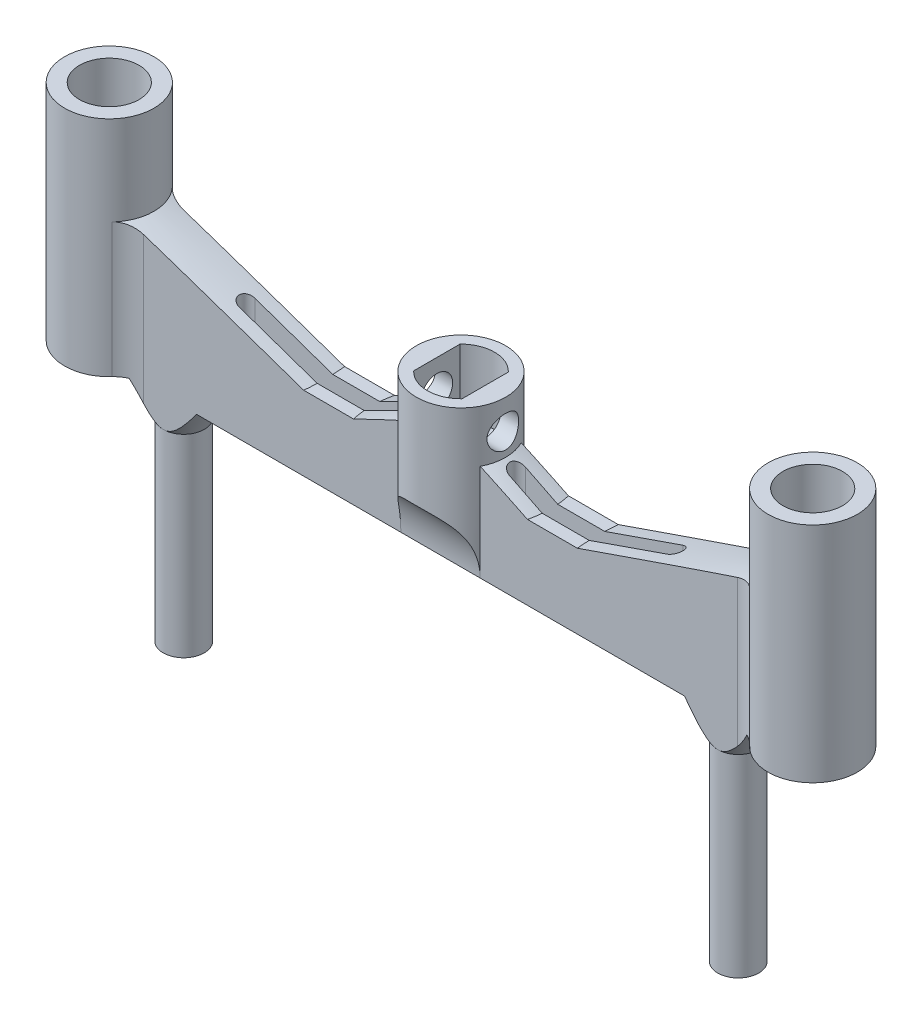
SolidWorks part; units mm, degrees
ref_plane "Front Plane" through (0, 0, 0) normal (0, 0, 1) x (1, 0, 0)
ref_plane "Top Plane" through (0, 0, 0) normal (0, 1, 0) x (1, 0, 0)
ref_plane "Right Plane" through (0, 0, 0) normal (1, 0, 0) x (0, 0, -1)
sketch "Sketch1" plane through (0, 0, 0) normal (0, 1, 0) x (1, 0, 0)
  line L0 (0, 0) -> (-8.0623, 0) construction
  line L1 (37.25, -2.75) -> (37.25, 2.75) construction
  line L2 (0, 0) -> (0, 13.1499) construction
  line L3 (34.5, 0) -> (40, 0) construction
  line L4 (37.25, -2.75) -> (-37.25, -2.75) construction
  line L5 (37.25, 2.75) -> (-37.25, 2.75) construction
  circle A0 centre (-31.5, 0) radius 0.7937 construction
  circle A1 centre (-22.5, 0) radius 0.7937 construction
  circle A2 centre (-37.25, 0) radius 2.75
  circle A3 centre (-37.25, 0) radius 1 construction
  circle A4 centre (37.25, 0) radius 1 construction
  circle A5 centre (37.25, 0) radius 2.75
  circle A8 centre (-22.5, 0) radius 2.75 construction
  circle A9 centre (-13.5, 0) radius 0.7937 construction
  circle A10 centre (-13.5, 0) radius 2.75 construction
  circle A11 centre (-4.5, 0) radius 0.7937 construction
  circle A12 centre (-4.5, 0) radius 2.75 construction
  circle A13 centre (4.5, 0) radius 0.7937 construction
  circle A14 centre (-31.5, 0) radius 2.75 construction
  circle A15 centre (4.5, 0) radius 2.75 construction
  circle A16 centre (13.5, 0) radius 0.7937 construction
  circle A17 centre (13.5, 0) radius 2.75 construction
  circle A18 centre (22.5, 0) radius 0.7937 construction
  circle A19 centre (22.5, 0) radius 2.75 construction
  circle A20 centre (31.5, 0) radius 0.7937 construction
  circle A21 centre (31.5, 0) radius 2.75 construction
  dimension "D1" = 8
extrude "Boss-Extrude1" add sketch "Sketch1" along normal blind 30
ref_plane "Plane1" through (0, 30, 0) normal (0, 1, 0) x (-1, 0, 0)
sketch "Sketch2" plane through (0, 30, 0) normal (0, 1, 0) x (-1, 0, 0)
  line L0 (0, 0) -> (-8.0623, 0) construction
  line L1 (-47.25, -2.75) -> (-47.25, 2.75) construction
  line L2 (0, 0) -> (0, 6.1566) construction
  line L3 (47.25, -2.75) -> (47.25, 2.75) construction
  line L4 (-41.9173, 2.75) -> (41.9173, 2.75)
  line L5 (41.9173, -2.75) -> (-41.9173, -2.75)
  line L6 (7.5915, -1.0438) -> (28.75, -1.0438)
  line L7 (-28.75, 1.0437) -> (-7.5915, 1.0437)
  line L8 (28.75, 1.0437) -> (7.5915, 1.0437)
  line L9 (-7.5915, -1.0438) -> (-28.75, -1.0438)
  arc A0 (-28.75, 1.0437) -> (-28.75, -1.0438) centre (-28.75, 0) ccw
  arc A1 (7.5915, 1.0437) -> (7.5915, -1.0438) centre (7.5915, 0) ccw
  circle A2 centre (-47.25, 0) radius 4
  arc A3 (-7.5915, 1.0437) -> (-7.5915, -1.0438) centre (-7.5915, 0) cw
  arc A4 (41.9173, -2.75) -> (41.9173, 2.75) centre (47.25, 0) ccw
  arc A5 (-41.9173, -2.75) -> (-41.9173, 2.75) centre (-47.25, 0) cw
  arc A8 (28.75, 1.0437) -> (28.75, -1.0438) centre (28.75, 0) cw
  circle A26 centre (47.25, 0) radius 4
extrude "Boss-Extrude2" add sketch "Sketch2" along normal blind 10
ref_plane "Plane2" through (0, 40, 0) normal (0, 1, 0) x (-1, 0, 0)
sketch "Sketch3" plane through (0, 40, 0) normal (0, 1, 0) x (-1, 0, 0)
  line L1 (3.25, -3.1125) -> (3.25, 3.1125) construction
  line L2 (-3.25, -3.1125) -> (-3.25, 3.1125) construction
  arc A0 (3.25, 3.1125) -> (-3.25, 3.1125) centre (0, 0) ccw construction
  circle A1 centre (0, 0) radius 6
  arc A2 (3.25, -3.1125) -> (-3.25, -3.1125) centre (0, 0) cw construction
extrude "Boss-Extrude3" add sketch "Sketch3" along normal blind 1
ref_plane "Plane3" through (0, 0, 0) normal (0, -1, 0) x (1, 0, 0)
hole_wizard "M3x0.5 Tapped Hole4" positions "Sketch28" profile "Sketch27" tap size "M3x0.5" standard "Ansi Metric"
sketch "Sketch28" plane through (0, 0, 0) normal (0, -1, 0) x (1, 0, 0)
  point P0 (37.25, 0)
sketch "Sketch27" plane through (37.25, 0, 0) normal (1, 0, 0) x (0, 0, -1)
  line L0 (0, 0) -> (0, 9.2511)
  line L1 (0, 9.2511) -> (1.25, 8.5)
  line L2 (1.25, 8.5) -> (1.25, 0)
  line L5 (1.25, 0) -> (0, 0)
  line L10 (0, 9.2511) -> (-1.25, 8.5) construction
  line L11 (0, -6.35) -> (0, 107.95) construction
  dimension "Tap Drill Dia." = 2.5
  dimension "Tap Drill Depth" = 8.5
  dimension "Drill Angle" = 118
cosmetic thread "Hole Thread5" parameters "D1"=6, "D2"=3
hole_wizard "M3x0.5 Tapped Hole5" positions "Sketch31" profile "Sketch30" tap size "M3x0.5" standard "Ansi Metric"
sketch "Sketch31" plane through (0, 0, 0) normal (0, -1, 0) x (1, 0, 0)
  point P0 (-37.25, 0)
sketch "Sketch30" plane through (-37.25, 0, 0) normal (1, 0, 0) x (0, 0, -1)
  line L0 (0, 0) -> (0, 9.2511)
  line L1 (0, 9.2511) -> (1.25, 8.5)
  line L2 (1.25, 8.5) -> (1.25, 0)
  line L5 (1.25, 0) -> (0, 0)
  line L10 (0, 9.2511) -> (-1.25, 8.5) construction
  line L11 (0, -6.35) -> (0, 107.95) construction
  dimension "Tap Drill Dia." = 2.5
  dimension "Tap Drill Depth" = 8.5
  dimension "Drill Angle" = 118
cosmetic thread "Hole Thread6" parameters "D1"=6, "D2"=3
ref_plane "Plane4" through (0, 41, 0) normal (0, 1, 0) x (-1, 0, 0)
sketch "Sketch33" plane through (0, 41, 0) normal (0, 1, 0) x (-1, 0, 0)
  line L1 (3.25, -3.1125) -> (3.25, 3.1125)
  line L2 (-3.25, -3.1125) -> (-3.25, 3.1125)
  arc A0 (3.25, 3.1125) -> (-3.25, 3.1125) centre (0, 0) ccw
  circle A1 centre (0, 0) radius 6
  arc A2 (3.25, -3.1125) -> (-3.25, -3.1125) centre (0, 0) cw
extrude "Boss-Extrude4" add sketch "Sketch33" along normal blind 9
fillet "Fillet2" radius 10 2 edges at (0, 40, -2.75) (0, 40, 2.75)
sketch "Sketch34" plane through (0, 0, 0) normal (1, 0, 0) x (0, 0, -1)
  line L0 (-3.1125, 50) -> (3.1125, 50) construction
  circle A0 centre (0, 50) radius 4 construction
  circle A1 centre (0, 46) radius 2.125
  dimension "D1" = 4.25
extrude "Cut-Extrude2" cut sketch "Sketch34" against normal mid plane 20
chamfer "Chamfer16" distance 4 distance2 2.5 4 edges at (-40, 30, 0) (-34.5, 30, 0) (40, 30, 0) (34.5, 30, 0) first distance on face at (-37.25, 30, 0) first distance on face at (37.25, 30, 0)
sketch "Sketch36" plane through (0, 40, 0) normal (0, 1, 0) x (-1, 0, 0)
  line L0 (0, 0) -> (0, 11.9399) construction
  circle A0 centre (-47.25, 0) radius 4
  circle A1 centre (-47.25, 0) radius 6
  circle A2 centre (47.25, 0) radius 6
  circle A3 centre (47.25, 0) radius 4
extrude "Boss-Extrude6" add sketch "Sketch36" along normal blind 20
fillet "Fillet5" radius 4 4 edges at (41.9173, 35, 2.75) (-41.9173, 35, 2.75) (-41.9173, 35, -2.75) (41.9173, 35, -2.75)
chamfer "Chamfer17" distance 23 distance2 8 2 edges at (41.25, 40, 0) (-41.25, 40, 0) first distance on face at (18.1707, 40, 0) first distance on face at (-18.1707, 40, 0)
chamfer "Chamfer18" distance 6 distance2 3 2 edges at (-6, 40, 0) (6, 40, 0) first distance on face at (-12.3432, 40, 0) first distance on face at (12.3432, 40, 0)
